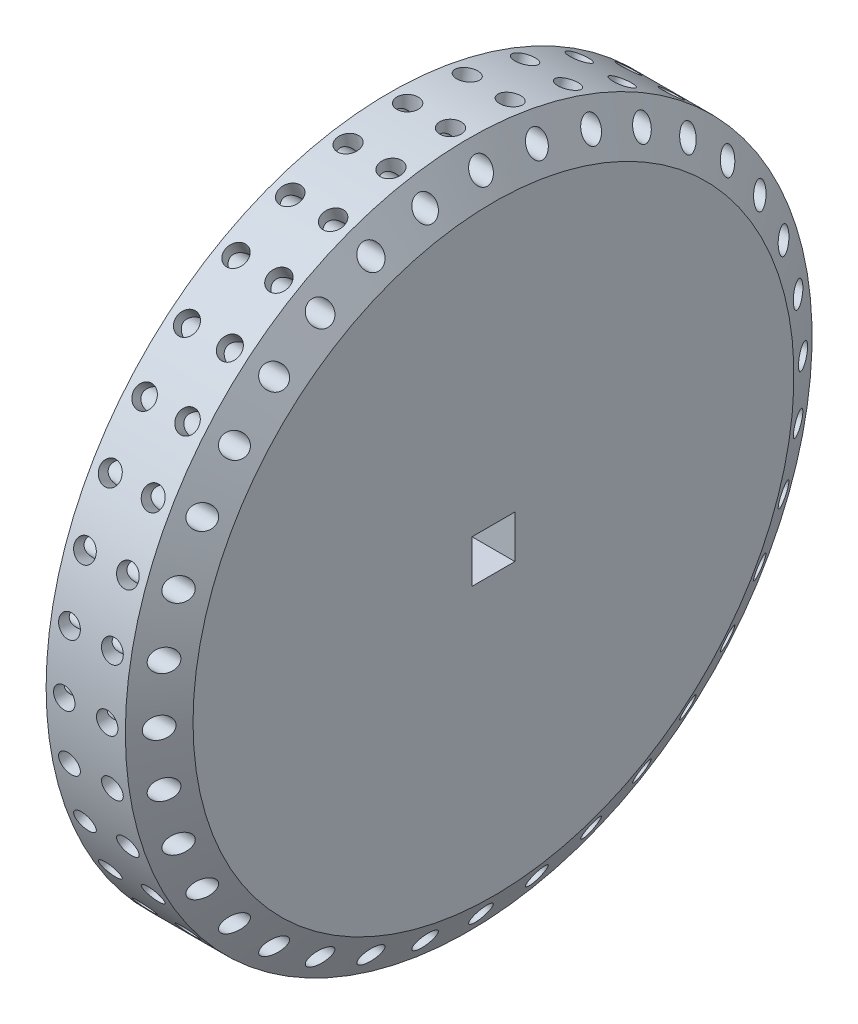
SolidWorks part; units mm, degrees
ref_plane "Front Plane" through (0, 0, 0) normal (0, 0, 1) x (1, 0, 0)
ref_plane "Top Plane" through (0, 0, 0) normal (0, 1, 0) x (1, 0, 0)
ref_plane "Right Plane" through (0, 0, 0) normal (1, 0, 0) x (0, 0, -1)
sketch "Sketch1" plane through (0, 0, 0) normal (0, 0, 1) x (1, 0, 0)
  line L0 (0, 0) -> (0, 6.35)
  line L1 (0, 6.35) -> (3.175, 12.7)
  line L2 (3.175, 12.7) -> (3.175, 25.4)
  line L3 (3.175, 25.4) -> (12.7, 25.4)
  line L4 (12.7, 25.4) -> (12.7, 0)
  line L5 (12.7, 0) -> (0, 0)
  line L6 (12.7, 0) -> (24.689, 0) construction
  dimension "D1" = 50.8
  dimension "D2" = 12.7
  dimension "D3" = 9.525
  dimension "D4" = 3.175
  dimension "D5" = 6.35
revolve "Revolve1" add sketch "Sketch1" angle 360 about L6
sketch "Sketch2" plane through (12.7, 0, 0) normal (1, 0, 0) x (0, 0, -1)
  line L0 (0, 23.8125) -> (0, 25.4) construction
  circle A0 centre (0, 23.8125) radius 0.7937
  circle A1 centre (0, 0) radius 25.4 construction
  dimension "D1" = 1.5875
  dimension "D2" = 1.5875
extrude "Cut-Extrude1" cut sketch "Sketch2" against normal through all
ref_plane "Plane1" through (0, 25.4, 0) normal (0, 1, 0) x (1, 0, 0)
sketch "Sketch3" plane through (0, 25.4, 0) normal (0, 1, 0) x (1, 0, 0)
  line L0 (6.35, 0) -> (9.525, 0) construction
  line L1 (9.525, 0) -> (12.7, 0) construction
  line L2 (12.7, -25.4) -> (12.7, 25.4) construction
  line L3 (6.35, 0) -> (3.175, 0) construction
  line L4 (3.175, 25.4) -> (3.175, -25.4) construction
  circle A0 centre (9.525, 0) radius 0.7937
  circle A1 centre (6.35, 0) radius 0.7937
  dimension "D1" = 3.175
  dimension "D2" = 1.5875
extrude "Cut-Extrude2" cut sketch "Sketch3" against normal up to next
chamfer "Chamfer1" distance 3.175 angle 30 1 edges at (12.7, 0, 25.4) first distance on face at (12.7, 23.8125, -0.7937)
chamfer "Chamfer2" distance 3.175 angle 30 1 edges at (3.175, 0, 25.4) first distance on face at (3.175, 23.8125, -0.7937)
pattern_circular "CirPattern1" count 36 over 360 about axis through (12.7, 0, 0) along (-1, 0, 0) of "Cut-Extrude2", "Cut-Extrude1"
sketch "Sketch4" plane through (0, 0, 0) normal (-1, 0, 0) x (0, 0, 1)
  line L1 (-1.5875, -1.5875) -> (1.5875, -1.5875)
  line L2 (-1.5875, -1.5875) -> (-1.5875, 1.5875)
  line L3 (-1.5875, 1.5875) -> (1.5875, 1.5875)
  line L4 (1.5875, -1.5875) -> (1.5875, 1.5875)
  line L5 (-1.5875, -1.5875) -> (1.5875, 1.5875) construction
  line L6 (-1.5875, 1.5875) -> (1.5875, -1.5875) construction
  point P0 (0, 0)
  dimension "D1" = 3.175
extrude "Cut-Extrude3" cut sketch "Sketch4" against normal up to next
sketch "Sketch5" plane through (0, 0, 0) normal (-1, 0, 0) x (0, 0, 1)
  line L1 (-3.175, -3.175) -> (3.175, -3.175)
  line L2 (-3.175, -3.175) -> (-3.175, 3.175)
  line L3 (-3.175, 3.175) -> (3.175, 3.175)
  line L4 (3.175, -3.175) -> (3.175, 3.175)
  line L5 (-3.175, -3.175) -> (3.175, 3.175) construction
  line L6 (-3.175, 3.175) -> (3.175, -3.175) construction
  point P0 (0, 0)
  dimension "D1" = 6.35
extrude "Cut-Extrude4" cut sketch "Sketch5" against normal blind 5.334
sketch "Sketch6" plane through (0, 0, 0) normal (-1, 0, 0) x (0, 0, 1)
  circle A0 centre (0, 0) radius 5.08
  dimension "D1" = 10.16
extrude "Cut-Extrude5" cut sketch "Sketch6" against normal blind 1.27
